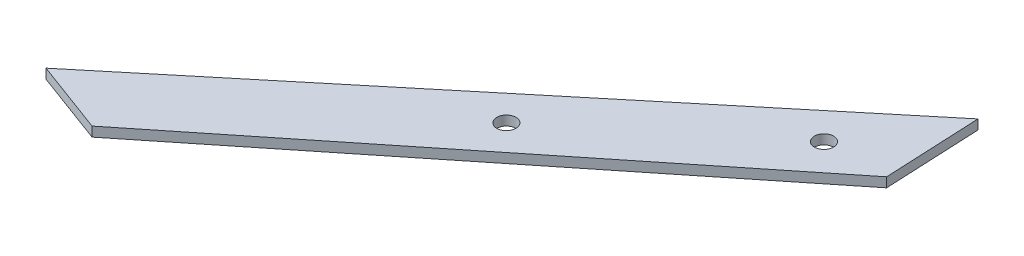
SolidWorks part; units mm, degrees
ref_plane "Front Plane" through (0, 0, 0) normal (0, 0, 1) x (1, 0, 0)
ref_plane "Top Plane" through (0, 0, 0) normal (0, 1, 0) x (1, 0, 0)
ref_plane "Right Plane" through (0, 0, 0) normal (1, 0, 0) x (0, 0, -1)
sketch "Sketch1" plane through (0, 0, 0) normal (0, 1, 0) x (1, 0, 0)
  line L0 (0, 0) -> (-56.2554, 20.8646)
  line L1 (0, 0) -> (-3.006, 64.9305)
  line L2 (-56.2554, 20.8646) -> (-3.006, 64.9305)
  dimension "D1" = 60
  dimension "D2" = 65
  dimension "D3" = 67
extrude "Boss-Extrude1" add sketch "Sketch1" along normal blind 1
ref_plane "Plane1" through (0, 0.5, 0) normal (0, 1, 0) x (1, 0, 0)
sketch "Sketch2" plane through (0, 1, 0) normal (0, 1, 0) x (1, 0, 0)
  line L0 (0, 0) -> (-1.1574, 25)
  line L1 (0, 0) -> (-3.006, 64.9305) construction
  line L2 (0, 0) -> (-23.4397, 8.6936)
  line L3 (-56.2554, 20.8646) -> (0, 0) construction
  arc A0 (-23.4397, 8.6936) -> (-1.1574, 25) centre (-4.3628, 6.0027) cw
  dimension "D1" = 25
  dimension "D2" = 25
extrude "Cut-Extrude1" cut sketch "Sketch2" against normal blind 1
sketch "Sketch3" plane through (0, 1, 0) normal (0, 1, 0) x (1, 0, 0)
  line L4 (-56.2554, 20.8646) -> (-3.006, 64.9305)
  line L5 (-56.2554, 20.8646) -> (-55.3178, 20.5169)
  line L6 (-56.2554, 20.8646) -> (-23.4397, 8.6936) construction
  line L7 (-3.006, 64.9305) -> (-2.9597, 63.9305)
  line L8 (-1.1574, 25) -> (-3.006, 64.9305) construction
  arc A4 (-55.3178, 20.5169) -> (-2.9597, 63.9305) centre (186.965, -218.4039) cw
  dimension "D1" = 1
  dimension "D2" = 1
extrude "Cut-Extrude3" cut sketch "Sketch3" against normal blind 0.5 rebuild error yes
sketch "Sketch4" plane through (0, 1, 0) normal (0, 1, 0) x (1, 0, 0)
  line L0 (-34.083, 12.6411) -> (-1.8253, 39.4263)
  line L1 (-56.2554, 20.8646) -> (-23.4397, 8.6936) construction
  line L2 (-1.1574, 25) -> (-3.006, 64.9305) construction
  line L3 (-48.6156, 18.0311) -> (-2.5428, 54.9263)
  line L4 (-48.6156, 18.0311) -> (-34.083, 12.6411)
  line L5 (-2.5428, 54.9263) -> (-1.8253, 39.4263)
  dimension "D1" = 15.5
  dimension "D2" = 15.5
extrude "Cut-Extrude4" cut sketch "Sketch4" against normal blind 10 body kept at (-48.6156, 0, -18.0311)
sketch "Sketch5" plane through (0, 1, 0) normal (0, 1, 0) x (1, 0, 0)
  line L0 (-29.6307, 42.8975) -> (-24.9159, 37.0099) construction
  line L1 (-3.006, 64.9305) -> (-56.2554, 20.8646) construction
  line L2 (-2.5428, 54.9263) -> (-48.6156, 18.0311) construction
  circle A0 centre (-27.2733, 39.9537) radius 1
  dimension "D1" = 2
extrude "Cut-Extrude5" cut sketch "Sketch5" against normal blind 10
sketch "Sketch7" plane through (0, 1, 0) normal (0, 1, 0) x (1, 0, 0)
  line L0 (-11.469, 57.927) -> (-6.5173, 51.7436) construction
  line L1 (-3.006, 64.9305) -> (-56.2554, 20.8646) construction
  line L2 (-2.5428, 54.9263) -> (-48.6156, 18.0311) construction
  circle A0 centre (-8.9931, 54.8353) radius 1
  dimension "D1" = 2
extrude "Cut-Extrude7" cut sketch "Sketch7" against normal blind 8
